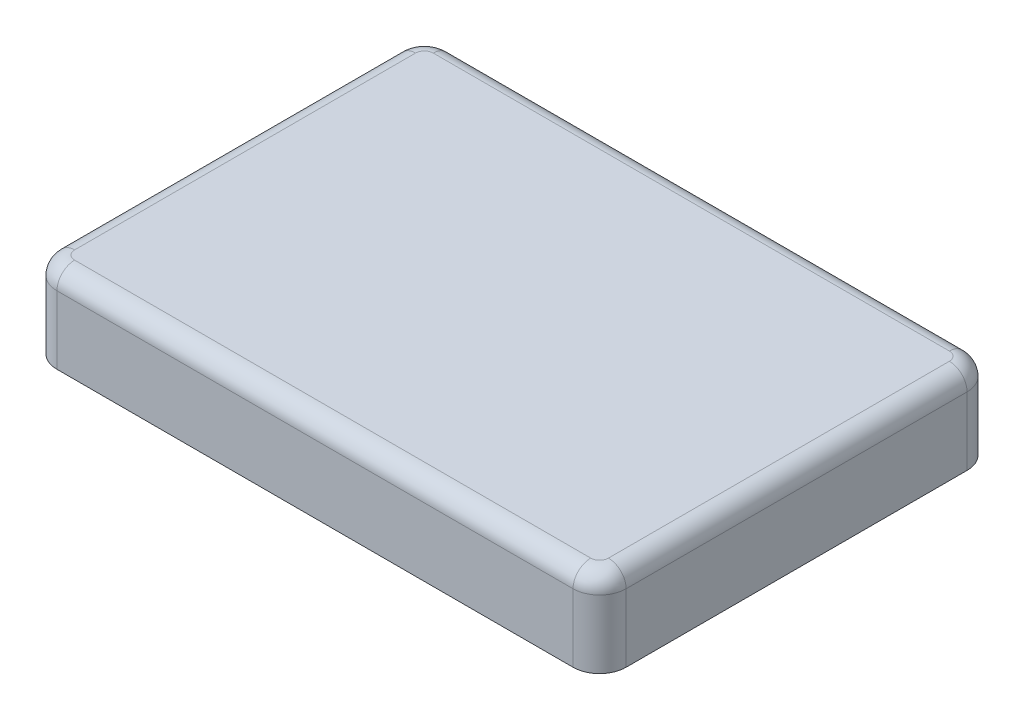
SolidWorks part; units mm, degrees
ref_plane "Front Plane" through (0, 0, 0) normal (0, 0, 1) x (1, 0, 0)
ref_plane "Top Plane" through (0, 0, 0) normal (0, 1, 0) x (1, 0, 0)
ref_plane "Right Plane" through (0, 0, 0) normal (1, 0, 0) x (0, 0, -1)
sketch "Sketch1" plane through (0, 0, 0) normal (0, 1, 0) x (1, 0, 0)
  line L0 (-41.5, -32.95) -> (-41.5, 24.85)
  line L1 (-37, -35.95) -> (50.5, -35.95)
  line L2 (-40, -32.95) -> (-40, 24.85)
  line L3 (-37, 27.85) -> (50.5, 27.85)
  line L4 (53.5, -32.95) -> (53.5, 24.85)
  line L5 (-40, -35.95) -> (53.5, 27.85) construction
  line L6 (-40, 27.85) -> (53.5, -35.95) construction
  line L7 (-37, 29.35) -> (50.5, 29.35)
  line L8 (55, -32.95) -> (55, 24.85)
  line L9 (-37, -37.45) -> (50.5, -37.45)
  line L10 (55, 24.85) -> (55, -32.95) construction
  line L11 (-41.5, -32.95) -> (-41.5, -26) construction
  line L16 (-37, 29.35) -> (50.5, 29.35) construction
  line L17 (50.5, -37.45) -> (-37, -37.45) construction
  arc A0 (50.5, -35.95) -> (53.5, -32.95) centre (50.5, -32.95) ccw
  arc A1 (-37, -35.95) -> (-40, -32.95) centre (-37, -32.95) cw
  arc A2 (-40, 24.85) -> (-37, 27.85) centre (-37, 24.85) cw
  arc A3 (50.5, 27.85) -> (53.5, 24.85) centre (50.5, 24.85) cw
  arc A4 (-41.5, 24.85) -> (-37, 29.35) centre (-37, 24.85) cw
  arc A5 (50.5, 29.35) -> (55, 24.85) centre (50.5, 24.85) cw
  arc A6 (50.5, -37.45) -> (55, -32.95) centre (50.5, -32.95) ccw
  arc A7 (-37, -37.45) -> (-41.5, -32.95) centre (-37, -32.95) cw
  dimension "D1" = 3
  dimension "D2" = 1.5
extrude "Boss-Extrude1" add sketch "Sketch1" along normal blind 1.25 contours A7 L9 A6 L8 A5 L7 A4 L0 L3 A3 L4 A0 L1 A1 L2 A2 | A3 L3 A2 L2 A1 L1 A0 L4 region at (-40.3264, 0, 4.05) region at (6.75, 0, 4.05)
extrude "Boss-Extrude2" add sketch "Sketch1<3>" against normal up to surface (13.28 mm away)
sketch "Sketch1<3>" plane through (0, 0, 0) normal (0, 1, 0) x (1, 0, 0) same geometry as "Sketch1"
sketch "Sketch2" plane through (0, 0, -29.35) normal (0, 0, -1) x (-1, 0, 0)
  line L5 (13.1593, -13.28) -> (-41.2921, -13.28)
  line L6 (13.1593, -13.28) -> (13.1593, -0.25)
  line L7 (13.1593, -0.25) -> (-41.2921, -0.25)
  line L30 (-41.2921, -13.28) -> (-41.2921, -0.25)
  line L33 (-40.7921, -13.28) -> (-40.7921, -0.75) construction
  line L37 (37, -13.28) -> (-50.5, -13.28) construction
  line L40 (-27.5421, -0.75) -> (-40.7921, -0.75) construction
  line L41 (12.6593, -13.28) -> (12.6593, -0.75) construction
  dimension "D2" = 0.5
  dimension "D3" = 0.5
  dimension "D1" = 0.5
extrude "Cut-Extrude1" cut sketch "Sketch2" against normal up to next
sketch "Sketch6" plane through (-41.5, 0, 0) normal (-1, 0, 0) x (0, 0, 1)
  line L0 (-24.85, -13.28) -> (32.95, -13.28) construction
  line L1 (-26.45, -8.78) -> (-9.45, -8.78)
  line L2 (-26.45, -8.78) -> (-26.45, -13.28)
  line L3 (-26.45, -13.28) -> (-9.45, -13.28)
  line L4 (-9.45, -8.78) -> (-9.45, -13.28)
  line L5 (-26.45, -13.28) -> (-26.45, -23.58) construction
  line L6 (-6.25, -13.28) -> (7.95, -13.28)
  line L7 (-6.25, -13.28) -> (-6.25, -7.28)
  line L8 (-6.25, -7.28) -> (7.95, -7.28)
  line L9 (7.95, -13.28) -> (7.95, -7.28)
  line L10 (11.8, -13.28) -> (26, -13.28)
  line L11 (11.8, -13.28) -> (11.8, -7.28)
  line L12 (11.8, -7.28) -> (26, -7.28)
  line L13 (26, -13.28) -> (26, -7.28)
  line L14 (-25.95, -9.28) -> (-9.95, -9.28) construction
  line L15 (-5.75, -7.78) -> (7.45, -7.78) construction
  line L16 (12.3, -7.78) -> (25.5, -7.78) construction
  dimension "D1" = 0.5
  dimension "D2" = 0.5
  dimension "D3" = 0.5
extrude "Cut-Extrude4" cut sketch "Sketch6" against normal up to next
sketch "Sketch7" plane through (0, -13.28, 0) normal (0, -1, 0) x (1, 0, 0)
  line L0 (53.5, -20.5506) -> (49.7006, -20.5506)
  line L1 (53.5, 32.95) -> (53.5, -24.85) construction
  line L2 (46.2006, -24.0506) -> (46.2006, -27.85)
  line L4 (50.5, -27.85) -> (41.2921, -27.85) construction
  line L5 (46.2006, -27.85) -> (50.5, -27.85)
  line L6 (53.5, -24.85) -> (53.5, -20.5506)
  line L7 (-37, 35.95) -> (-32.7006, 35.95)
  line L8 (-37, 35.95) -> (50.5, 35.95) construction
  line L9 (-32.7006, 35.95) -> (-32.7006, 32.1506)
  line L10 (-36.2006, 28.6506) -> (-40, 28.6506)
  line L11 (-40, 26) -> (-40, 32.95) construction
  line L12 (-40, 28.6506) -> (-40, 32.95)
  circle A0 centre (49.7006, -24.0506) radius 1.5
  arc A1 (49.7006, -20.5506) -> (46.2006, -24.0506) centre (49.7006, -24.0506) ccw
  arc A2 (50.5, -27.85) -> (53.5, -24.85) centre (50.5, -24.85) ccw
  circle A3 centre (-36.2006, 32.1506) radius 1.5
  arc A4 (-32.7006, 32.1506) -> (-36.2006, 28.6506) centre (-36.2006, 32.1506) cw
  arc A5 (-40, 32.95) -> (-37, 35.95) centre (-37, 32.95) cw
  circle A6 centre (49.7006, -24.0506) radius 1.6 construction
  arc A7 (49.7006, -20.5506) -> (46.2006, -24.0506) centre (49.7006, -24.0506) ccw construction
  dimension "D1" = 3
extrude "Boss-Extrude3" add sketch "Sketch7" against normal up to next
fillet "Fillet1" radius 3 4 edges at (-32.7006, -6.64, 35.95) (-40, -6.64, 28.6506) (46.2006, -6.64, -27.85) (53.5, -6.64, -20.5506)
fillet "Fillet2" radius 3 24 edges at (52.6213, 0, 35.0713) (53.5, 0, 7.6997) (52.6213, 0, -19.6719) (50.1003, 0, -20.5506) (47.2257, 0, -21.5757) (46.2006, 0, -24.4503) (45.3219, 0, -26.9713) (3.1003, 0, -27.85) (-39.1213, 0, -26.9713) (-40, 0, 0.4003) (-39.1213, 0, 27.7719) (-36.6003, 0, 28.6506) (-33.7257, 0, 29.6757) (-32.7006, 0, 32.5503) (-31.8219, 0, 35.0713) (10.3997, 0, 35.95) (-41.5, 1.25, 4.05) (-40.182, 1.25, -28.032) (6.75, 1.25, -29.35) (53.682, 1.25, -28.032) (55, 1.25, 4.05) (53.682, 1.25, 36.132) (6.75, 1.25, 37.45) (-40.182, 1.25, 36.132)
